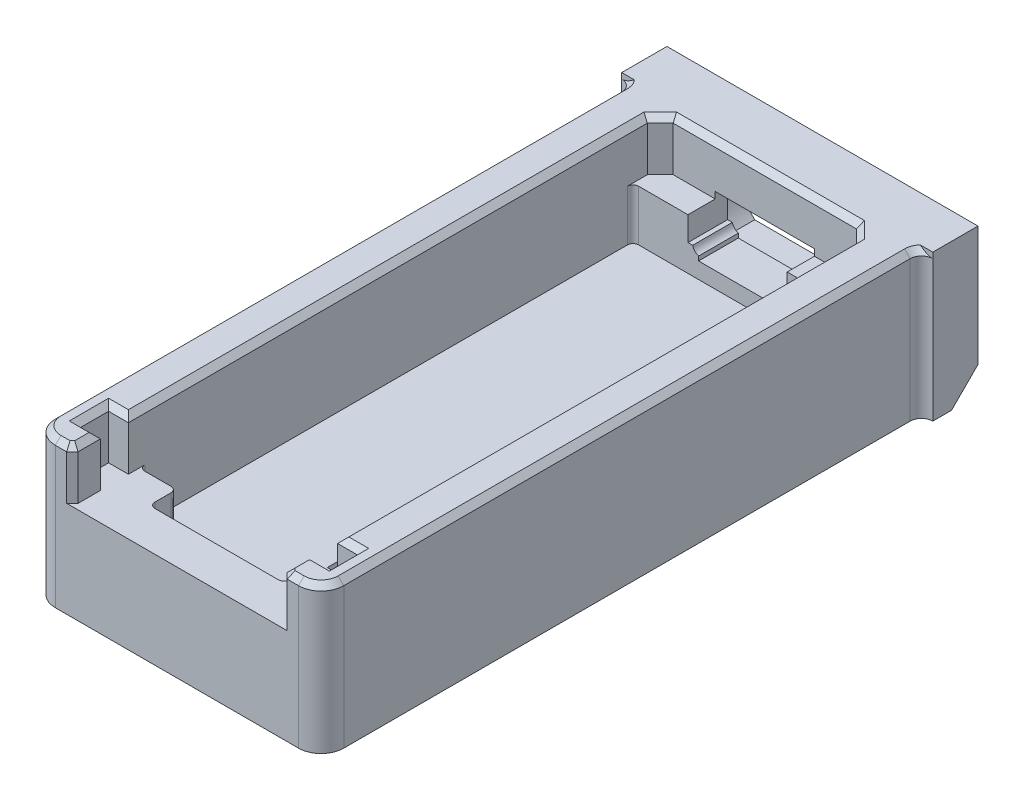
SolidWorks part; units mm, degrees
ref_plane "Front Plane" through (0, 0, 0) normal (0, 0, 1) x (1, 0, 0)
ref_plane "Top Plane" through (0, 0, 0) normal (0, 1, 0) x (1, 0, 0)
ref_plane "Right Plane" through (0, 0, 0) normal (1, 0, 0) x (0, 0, -1)
sketch "Sketch2" plane through (15.9134, 30.6185, 37.0903) normal (1, 0, 0) x (0, 0, 1)
  line L0 (116.2262, -14.5431) -> (116.2262, 10)
  line L1 (116.2262, 10) -> (-29.35, 10)
  line L2 (-29.35, 10) -> (-29.35, -22.1724)
  line L3 (-29.35, -22.1724) -> (116.2262, -14.5431)
  line L4 (-61.6865, -4.4906) -> (-8.9589, -1.7273) construction
  line L5 (104.9423, -11.6296) -> (97.9519, -11.996) construction
  line L7 (87.1415, -12.4624) -> (72.162, -13.2474) construction
  line L8 (21.59, -17.5) -> (-21.59, -17.5) construction
  line L9 (21.59, -17.5) -> (21.59, -2.5) construction
  line L10 (21.59, -2.5) -> (-21.59, -2.5) construction
  line L11 (-21.59, -17.5) -> (-21.59, -2.5) construction
  line L12 (21.09, -2.5) -> (19.55, -2.5) construction
  line L13 (112.2262, -12.75) -> (112.2262, 6) construction
  line L14 (112.2262, 6) -> (-25.35, 6) construction
  line L15 (21.59, 0) -> (21.59, -2.5) construction
  line L16 (-21.59, 0) -> (-21.59, -2.5) construction
  line L18 (87.0734, -11.1642) -> (87.2095, -13.7606) construction
  line L19 (87.0734, -11.1642) -> (72.094, -11.9492) construction
  line L20 (87.2095, -13.7606) -> (72.2301, -14.5457) construction
  line L21 (72.094, -11.9492) -> (72.2301, -14.5457) construction
  line L22 (80.7932, -12.4747) -> (87.1247, -12.1428) construction
  line L24 (21.7261, -12.5361) -> (21.59, -9.9396) construction
  line L25 (21.7261, -12.5361) -> (36.7055, -11.751) construction
  line L26 (21.59, -9.9396) -> (36.5694, -9.1546) construction
  line L27 (36.7055, -11.751) -> (36.5694, -9.1546) construction
  line L28 (37.3995, -10.6632) -> (29.9098, -11.0557) construction
  line L30 (-25.35, 6) -> (-25.35, -19.96) construction
  line L31 (36.6375, -10.4528) -> (21.658, -11.2379) construction
  line L32 (29.8941, -10.7562) -> (29.8993, -10.856) construction
  line L33 (69.094, -2.4418) -> (69.094, -6.4491) construction
  line L34 (21.0682, 9.5) -> (21.3918, 9.5) construction
  line L35 (-25.35, 4.3272) -> (-25.35, 4.1272) construction
  line L36 (112.2262, -14.5431) -> (112.2262, 6) construction
  line L37 (-25.35, 6) -> (-25.35, -22.1724) construction
  line L38 (-25.35, -19.96) -> (112.2262, -12.75) construction
  line L39 (-29.4547, -20.1751) -> (116.1215, -12.5458) construction
  point P42 (29.8967, -10.8061)
  dimension "D2" = 32.5246
  dimension "D3" = 4
  dimension "D4" = 15
  dimension "D5" = 15
  dimension "D6" = 2.6
  dimension "D7" = 0.5
  dimension "D9" = 10.82
  dimension "D10" = 0.8318
  dimension "D11" = 7
  dimension "D12" = 0.3
  dimension "D13" = 3
  dimension "D14" = 0.5
  dimension "D8" = 2
extrude "Boss-Extrude1" add sketch "Sketch2" along normal mid plane 48
shell "Shell1" thickness 4 removed face at (15.9134, 48.9763, 80.5284)
fillet "Fillet1" radius 4 4 edges at (-8.0866, 36.7047, 7.7403) (39.9134, 36.7047, 7.7403) (-8.0866, 32.8901, 153.3164) (39.9134, 32.8901, 153.3164)
chamfer "Chamfer1" distance 2.3431 angle 45 8 edges at (-6.915, 20.6185, 152.1449) (15.9134, 20.6185, 153.3164) (38.7418, 20.6185, 152.1449) (39.9134, 20.6185, 80.5284) (38.7418, 20.6185, 8.9118) (15.9134, 20.6185, 7.7403) (-6.915, 20.6185, 8.9118) (-8.0866, 20.6185, 80.5284)
sketch "Sketch3" plane through (0, 24.6185, 0) normal (0, 1, 0) x (1, 0, 0)
  line L0 (18.8534, -58.0703) -> (18.3534, -58.0703) construction
  line L1 (18.1034, -57.8203) -> (19.1034, -57.8203)
  line L2 (18.1034, -57.8203) -> (18.1034, -58.8203)
  line L3 (18.1034, -58.8203) -> (19.1034, -58.8203)
  line L4 (19.1034, -57.8203) -> (19.1034, -58.8203)
  line L5 (18.8534, -58.5703) -> (18.8534, -58.0703) construction
  line L6 (20.6434, -57.8203) -> (20.6434, -58.8203)
  line L7 (20.6434, -57.8203) -> (21.6434, -57.8203)
  line L8 (21.6434, -57.8203) -> (21.6434, -58.8203)
  line L9 (20.6434, -58.8203) -> (21.6434, -58.8203)
  line L10 (20.6434, -55.2803) -> (20.6434, -56.2803)
  line L11 (20.6434, -55.2803) -> (21.6434, -55.2803)
  line L12 (21.6434, -55.2803) -> (21.6434, -56.2803)
  line L13 (20.6434, -56.2803) -> (21.6434, -56.2803)
  line L14 (20.6434, -52.7403) -> (20.6434, -53.7403)
  line L15 (20.6434, -52.7403) -> (21.6434, -52.7403)
  line L16 (21.6434, -52.7403) -> (21.6434, -53.7403)
  line L17 (20.6434, -53.7403) -> (21.6434, -53.7403)
  line L18 (18.1034, -55.2803) -> (18.1034, -56.2803)
  line L19 (18.1034, -55.2803) -> (19.1034, -55.2803)
  line L20 (19.1034, -55.2803) -> (19.1034, -56.2803)
  line L21 (18.1034, -56.2803) -> (19.1034, -56.2803)
  line L22 (18.1034, -52.7403) -> (18.1034, -53.7403)
  line L23 (18.1034, -52.7403) -> (19.1034, -52.7403)
  line L24 (19.1034, -52.7403) -> (19.1034, -53.7403)
  line L25 (18.1034, -53.7403) -> (19.1034, -53.7403)
  line L26 (20.8934, -58.5703) -> (21.3934, -58.5703) construction
  line L27 (20.8934, -55.5303) -> (20.8934, -56.0303) construction
  point P4 (18.6034, -57.8203)
  point P7 (18.6034, -58.0703)
  point P8 (19.1034, -58.3203)
  point P11 (18.8534, -58.3203)
  point P12 (21.1434, -58.8203)
  point P35 (21.1434, -58.5703)
  point P36 (20.6434, -55.7803)
  point P39 (20.8934, -55.7803)
  dimension "D1" = 1
  dimension "D2" = 2
  dimension "D3" = 3
extrude "Cut-Extrude1" cut sketch "Sketch3" against normal offset from surface (3.5 mm away) 0.5 up to face at (15.9134, 20.6185, 80.5284)
sketch "Sketch4" plane through (0, 0, 7.7403) normal (0, 0, -1) x (-1, 0, 0)
  line L0 (-13.2434, 28.9458) -> (-18.5834, 28.9458) construction
  line L1 (-13.2434, 28.9458) -> (-18.5834, 28.9458) construction
  line L2 (-9.9134, 31.5685) -> (-15.9134, 37.5685) construction
  line L3 (-15.9134, 28.9458) -> (-15.9134, 37.5381) construction
  line L4 (-21.9134, 31.5685) -> (-9.9134, 31.5685)
  line L5 (-21.9134, 31.5685) -> (-21.9134, 24.1685) construction
  line L6 (-21.9134, 24.1685) -> (-9.9134, 24.1685)
  line L7 (-9.9134, 31.5685) -> (-9.9134, 24.1685) construction
  line L8 (-19.1134, 26.7913) -> (-18.5834, 28.9458) construction
  arc A0 (-19.5034, 27.1813) -> (-19.1134, 26.7913) centre (-19.1134, 27.1813) ccw construction
  arc A1 (-19.5034, 27.1813) -> (-19.1134, 26.7913) centre (-19.1134, 27.1813) ccw construction
  arc A2 (-12.7134, 26.7913) -> (-12.3234, 27.1813) centre (-12.7134, 27.1813) ccw construction
  arc A3 (-12.7134, 26.7913) -> (-12.3234, 27.1813) centre (-12.7134, 27.1813) ccw construction
  arc A4 (-9.9134, 24.1685) -> (-9.9134, 31.5685) centre (-13.6134, 27.8685) ccw
  arc A5 (-21.9134, 24.1685) -> (-21.9134, 31.5685) centre (-18.2134, 27.8685) cw
  point P12 (-15.9134, 31.5685)
  point P13 (-15.9134, 28.9458)
  point P17 (-21.9134, 27.8685)
  point P20 (-18.8484, 27.8685)
  dimension "D3" = 45
  dimension "D1" = 12
  dimension "D2" = 7.4
extrude "Cut-Extrude2" cut sketch "Sketch4" against normal up to surface (4 mm away) up to face at (15.9134, 38.5999, 11.7403)
sketch "Sketch5" plane through (0, 24.6185, 0) normal (0, 1, 0) x (1, 0, 0)
  line L0 (11.5234, -11.7403) -> (11.5234, -15.0865)
  line L1 (35.9134, -11.7403) -> (-4.0866, -11.7403) construction
  line L2 (23.9134, -61.0903) -> (7.9134, -61.0903) construction
  line L3 (11.5234, -15.2503) -> (7.1634, -15.2503)
  line L4 (6.6634, -15.7503) -> (6.6634, -58.4303)
  line L5 (7.1634, -58.9303) -> (9.4634, -58.9303)
  line L6 (9.9634, -59.4303) -> (9.9634, -60.8403)
  line L7 (10.4634, -61.3403) -> (21.3634, -61.3403)
  line L8 (26.6734, -64.8503) -> (5.1534, -64.8503)
  line L9 (3.1534, -62.8503) -> (3.1534, -12.7403)
  line L10 (2.1534, -11.7403) -> (11.5234, -11.7403)
  line L11 (6.9134, -60.0903) -> (6.9134, -14.0903) construction
  line L12 (9.0534, -15.5003) -> (7.5134, -15.5003) construction
  line L13 (15.9134, 2.8046) -> (15.9134, 8.9631) construction
  line L14 (35.9134, -7.7403) -> (-4.0866, -7.7403) construction
  line L15 (11.8234, -11.9003) -> (11.8234, -11.7403) construction
  line L16 (6.6634, -58.9303) -> (3.1534, -58.9303) construction
  line L17 (9.9634, -61.3403) -> (9.9634, -64.8503) construction
  line L18 (7.5134, -58.6803) -> (9.0534, -58.6803) construction
  line L19 (10.2134, -59.0903) -> (10.2134, -53.0903) construction
  line L20 (9.3434, -15.2503) -> (9.3434, -11.7403) construction
  line L21 (22.4834, -15.2503) -> (22.4834, -11.7403) construction
  line L22 (21.8634, -61.3403) -> (21.8634, -64.8503) construction
  line L23 (25.1634, -58.9303) -> (28.6734, -58.9303) construction
  line L24 (29.6734, -11.7403) -> (20.3034, -11.7403)
  line L25 (28.6734, -62.8503) -> (28.6734, -12.7403)
  line L28 (25.1634, -15.7503) -> (25.1634, -58.4303)
  line L29 (20.3034, -15.2503) -> (24.6634, -15.2503)
  line L30 (20.3034, -11.7403) -> (20.3034, -15.0865)
  line L31 (11.5234, -15.2503) -> (11.5234, -15.0865)
  line L32 (20.3034, -15.2503) -> (20.3034, -15.0865)
  line L33 (21.8634, -60.8403) -> (21.8634, -59.9938)
  line L34 (21.8634, -59.9938) -> (22.927, -58.9303)
  line L35 (22.927, -58.9303) -> (24.6634, -58.9303)
  line L36 (21.9134, -59.5903) -> (22.4134, -59.0903) construction
  arc A1 (7.1634, -15.2503) -> (6.6634, -15.7503) centre (7.1634, -15.7503) ccw
  arc A2 (6.6634, -58.4303) -> (7.1634, -58.9303) centre (7.1634, -58.4303) ccw
  arc A3 (9.4634, -58.9303) -> (9.9634, -59.4303) centre (9.4634, -59.4303) cw
  arc A4 (9.9634, -60.8403) -> (10.4634, -61.3403) centre (10.4634, -60.8403) ccw
  arc A5 (5.1534, -64.8503) -> (3.1534, -62.8503) centre (5.1534, -62.8503) cw
  arc A6 (3.1534, -12.7403) -> (2.1534, -11.7403) centre (2.1534, -12.7403) ccw
  arc A7 (28.6734, -12.7403) -> (29.6734, -11.7403) centre (29.6734, -12.7403) cw
  arc A8 (26.6734, -64.8503) -> (28.6734, -62.8503) centre (26.6734, -62.8503) ccw
  arc A9 (21.8634, -60.8403) -> (21.3634, -61.3403) centre (21.3634, -60.8403) cw
  arc A11 (25.1634, -58.4303) -> (24.6634, -58.9303) centre (24.6634, -58.4303) cw
  arc A12 (24.6634, -15.2503) -> (25.1634, -15.7503) centre (24.6634, -15.7503) cw
  point P9 (15.9134, -61.3403)
  point P18 (15.9134, -7.7403)
  point P77 (15.9134, -64.8503)
  dimension "D1" = 0.25
  dimension "D7" = 0.5
  dimension "D8" = 2
  dimension "D9" = 2
  dimension "D2" = 0.25
  dimension "D3" = 0.3
  dimension "D4" = 0.25
  dimension "D5" = 0.25
  dimension "D6" = 0.25
  dimension "D10" = 0.25
extrude "Boss-Extrude2" add sketch "Sketch5" along normal up to surface (4.5 mm away)
sketch "Sketch7" plane through (0, 0, 11.7403) normal (0, 0, -1) x (-1, 0, 0)
  line L1 (-20.3034, 24.6185) -> (-11.5234, 24.6185) construction
  line L2 (-20.3034, 24.6185) -> (-11.5234, 24.6185)
  line L3 (-19.3634, 26.0413) -> (-12.4634, 26.0413)
  line L4 (-11.5234, 26.9813) -> (-11.9388, 26.9813)
  line L5 (-11.5234, 29.1185) -> (-11.5234, 24.6185) construction
  line L6 (-15.9134, 24.6185) -> (-15.9134, 31.8855) construction
  line L7 (-18.9134, 26.2913) -> (-12.9134, 26.2913) construction
  line L9 (-12.7134, 26.5913) -> (-12.7134, 26.6313) construction
  line L10 (-12.4634, 26.0413) -> (-12.4634, 26.4214)
  line L11 (-12.1234, 27.1813) -> (-12.0234, 27.1813) construction
  line L12 (-11.5234, 26.9813) -> (-11.5234, 24.6185)
  line L13 (-20.3034, 26.9813) -> (-20.3034, 24.6185)
  line L14 (-19.3634, 26.0413) -> (-19.3634, 26.4214)
  line L15 (-20.3034, 26.9813) -> (-19.888, 26.9813)
  arc A1 (-19.3634, 26.4214) -> (-19.888, 26.9813) centre (-19.1134, 27.1813) cw
  arc A2 (-12.7134, 26.3813) -> (-11.9134, 27.1813) centre (-12.7134, 27.1813) ccw
  arc A3 (-12.4634, 26.4214) -> (-11.9388, 26.9813) centre (-12.7134, 27.1813) ccw
  point P7 (-15.9134, 24.6185)
  point P12 (-15.9134, 24.6185)
  point P30 (-15.9134, 26.0413)
  dimension "D1" = 0.25
  dimension "D3" = 0.25
  dimension "D4" = 0.2
  dimension "D2" = 0.25
extrude "Boss-Extrude5" add sketch "Sketch7" against normal up to surface (3.51 mm away) contours A1 L15 L13 L2 L12 L4 A3 L10 L3 L14 up to face at (9.3434, 26.8685, 15.2503)
sketch "Sketch9" plane through (0, 29.1185, 0) normal (0, 1, 0) x (1, 0, 0)
  line L0 (28.6734, -62.8503) -> (28.6734, -12.7403)
  line L1 (20.3034, -12.8403) -> (24.017, -12.8403)
  line L2 (24.017, -12.8403) -> (25.1634, -13.9867)
  line L3 (25.1634, -13.9867) -> (25.1634, -60.1938)
  line L5 (23.2945, -11.7403) -> (20.3034, -11.7403)
  line L6 (29.6734, -11.7403) -> (23.2945, -11.7403)
  line L7 (20.3034, -11.7403) -> (20.3034, -12.8403)
  line L8 (11.5234, -11.7403) -> (11.5234, -15.2503) construction
  line L9 (11.5234, -11.7403) -> (11.5234, -12.8403)
  line L10 (15.9134, -11.7403) -> (15.9134, -10.4554) construction
  line L11 (25.1634, -60.1938) -> (25.1634, -64.8503)
  line L12 (2.1534, -11.7403) -> (8.5323, -11.7403) construction
  line L13 (8.5323, -11.7403) -> (11.5234, -11.7403) construction
  line L14 (2.1534, -11.7403) -> (8.5323, -11.7403)
  line L15 (8.5323, -11.7403) -> (11.5234, -11.7403)
  line L16 (25.1634, -13.9867) -> (24.017, -12.8403)
  line L17 (25.1634, -60.1938) -> (25.1634, -13.9867)
  line L18 (24.017, -61.3403) -> (25.1634, -60.1938)
  line L19 (6.6634, -60.1938) -> (7.8098, -61.3403)
  line L20 (7.8098, -61.3403) -> (24.017, -61.3403)
  line L21 (6.6634, -13.9867) -> (6.6634, -60.1938)
  line L22 (7.8098, -12.8403) -> (6.6634, -13.9867)
  line L23 (24.017, -12.8403) -> (7.8098, -12.8403)
  line L29 (6.6634, -13.9867) -> (6.6634, -60.1938)
  line L30 (7.8098, -12.8403) -> (6.6634, -13.9867)
  line L31 (11.5234, -12.8403) -> (7.8098, -12.8403)
  line L32 (3.1534, -62.8503) -> (3.1534, -12.7403) construction
  line L33 (3.1534, -62.8503) -> (3.1534, -12.7403)
  line L35 (26.6734, -64.8503) -> (5.1534, -64.8503) construction
  line L36 (35.9134, -7.7403) -> (-4.0866, -7.7403) construction
  line L37 (25.1634, -64.8503) -> (26.6734, -64.8503)
  line L40 (6.6634, -60.1938) -> (6.6634, -64.8503)
  line L41 (6.6634, -64.8503) -> (5.1534, -64.8503)
  arc A0 (3.1534, -12.7403) -> (2.1534, -11.7403) centre (2.1534, -12.7403) ccw construction
  arc A1 (3.1534, -12.7403) -> (2.1534, -11.7403) centre (2.1534, -12.7403) ccw
  arc A2 (3.1534, -62.8503) -> (5.1534, -64.8503) centre (5.1534, -62.8503) ccw construction
  arc A3 (3.1534, -62.8503) -> (5.1534, -64.8503) centre (5.1534, -62.8503) ccw
  arc A4 (28.6734, -62.8503) -> (26.6734, -64.8503) centre (26.6734, -62.8503) cw
  arc A5 (28.6734, -12.7403) -> (29.6734, -11.7403) centre (29.6734, -12.7403) cw
  point P29 (15.9134, -7.7403)
  point P34 (15.9134, -64.8503)
  point P35 (15.9134, -61.3403)
  dimension "D1" = 0.25
extrude "Boss-Extrude6" add sketch "Sketch9" along normal offset from surface (4.45 mm away) 2 up to face at (15.9134, 31.5685, 9.7403) offset beyond the face yes
sketch "Sketch10" plane through (0, 0, 11.7403) normal (0, 0, -1) x (-1, 0, 0)
  line L0 (-20.3034, 31.5685) -> (-20.3034, 26.9813) construction
  line L1 (-20.3034, 33.5685) -> (-11.5234, 33.5685)
  line L2 (-20.3034, 33.5685) -> (-20.3034, 29.6958)
  line L3 (-20.3034, 29.6958) -> (-11.5234, 29.6958)
  line L4 (-11.5234, 33.5685) -> (-11.5234, 29.6958)
  line L5 (-11.5234, 31.5685) -> (-11.5234, 26.9813) construction
  line L6 (-11.5234, 33.5685) -> (-2.1534, 33.5685) construction
  line L7 (-13.4434, 29.4458) -> (-18.3834, 29.4458) construction
  dimension "D1" = 0.25
extrude "Boss-Extrude7" add sketch "Sketch10" against normal up to surface (1.1 mm away) up to face at (22.1602, 31.3435, 12.8403)
chamfer "Chamfer2" distance 0.5 angle 45 2 edges at (6.6634, 31.3435, 64.8503) (25.1634, 31.3435, 64.8503)
sketch "Sketch11" plane through (0, 33.5685, 0) normal (0, 1, 0) x (1, 0, 0)
  line L0 (22.007, -12.8403) -> (25.1634, -15.9967)
  line L1 (7.8098, -12.8403) -> (24.017, -12.8403) construction
  line L2 (25.1634, -13.9867) -> (25.1634, -64.3503) construction
  line L3 (24.017, -12.8403) -> (25.1634, -13.9867) construction
  line L4 (24.8134, -16.0003) -> (24.3134, -15.5003) construction
  line L5 (24.017, -12.8403) -> (25.1634, -13.9867)
  line L6 (25.1634, -13.9867) -> (25.1634, -15.9967)
  line L7 (22.007, -12.8403) -> (24.017, -12.8403)
  line L8 (15.9134, -11.7403) -> (15.9134, 3.1456) construction
  line L10 (35.9134, -11.7403) -> (-4.0866, -11.7403) construction
  line L11 (9.8198, -12.8403) -> (7.8098, -12.8403)
  line L12 (6.6634, -13.9867) -> (6.6634, -15.9967)
  line L13 (7.8098, -12.8403) -> (6.6634, -13.9867)
  line L14 (9.8198, -12.8403) -> (6.6634, -15.9967)
  point P13 (15.9134, -11.7403)
  dimension "D1" = 0.25
extrude "Boss-Extrude8" [suppressed] add sketch "Sketch11" against normal offset from surface (2.7 mm away) 0.25
sketch "Sketch12" plane through (0, 33.5685, 0) normal (0, 1, 0) x (1, 0, 0)
  line L0 (15.9134, -57.4103) -> (15.9134, -59.8903) construction
  line L7 (25.6634, -64.8503) -> (6.1634, -64.8503) construction
  line L9 (15.9134, -59.8903) -> (15.9134, -62.3703) construction
  line L10 (15.9134, -62.3703) -> (15.9134, -64.8503) construction
  line L11 (28.6734, -62.8503) -> (26.9184, -62.8503) construction
  line L12 (26.9184, -59.8903) -> (4.9084, -59.8903)
  line L13 (26.9184, -59.8903) -> (26.9184, -62.3703)
  line L14 (26.9184, -62.3703) -> (4.9084, -62.3703)
  line L15 (4.9084, -59.8903) -> (4.9084, -62.3703)
  line L16 (26.9184, -62.8503) -> (25.1634, -62.8503) construction
  line L17 (25.1634, -13.9867) -> (25.1634, -64.3503) construction
  line L18 (19.3734, -59.5903) -> (17.8334, -59.5903) construction
  point P16 (15.9134, -59.8903)
  dimension "D1" = 0.3
extrude "Cut-Extrude3" cut sketch "Sketch12" against normal up to surface (4.45 mm away) up to face at (15.9551, 29.1185, 60.9424)
chamfer "Chamfer3" distance 0.5 angle 45 23 edges at (28.9663, 33.5685, 12.0332) (28.6734, 33.5685, 37.7953) (28.0876, 33.5685, 64.2645) (26.1684, 33.5685, 64.8503) (6.4134, 33.5685, 64.6003) (25.4134, 33.5685, 64.6003) (25.1634, 33.5685, 63.3603) (26.0409, 33.5685, 62.3703) (26.9184, 33.5685, 61.1303) (26.0409, 33.5685, 59.8903) (25.1634, 33.5685, 36.9385) (15.9134, 33.5685, 12.8403) (6.6634, 33.5685, 36.9385) (5.7859, 33.5685, 59.8903) (4.9084, 33.5685, 61.1303) (5.7859, 33.5685, 62.3703) (6.6634, 33.5685, 63.3603) (5.6584, 33.5685, 64.8503) (3.7392, 33.5685, 64.2645) (3.1534, 33.5685, 37.7953) (2.8605, 33.5685, 12.0332) (24.5902, 33.5685, 13.4135) (7.2366, 33.5685, 13.4135)
sketch "Sketch13" plane through (0, 33.5685, 0) normal (0, 1, 0) x (1, 0, 0)
  line L0 (2.1534, -11.7403) -> (2.1534, -7.7403)
  line L1 (35.9134, -7.7403) -> (-4.0866, -7.7403) construction
  line L2 (2.1534, -7.7403) -> (29.6734, -7.7403)
  line L3 (29.6734, -7.7403) -> (29.6734, -11.7403)
  line L8 (35.9134, -11.7403) -> (29.6734, -11.7403)
  line L9 (28.6734, -12.7403) -> (28.6734, -62.8503)
  line L10 (26.6734, -64.8503) -> (5.1534, -64.8503)
  line L11 (3.1534, -62.8503) -> (3.1534, -12.7403)
  line L12 (2.1534, -11.7403) -> (-4.0866, -11.7403)
  line L13 (-4.0866, -11.7403) -> (-4.0866, -149.3164)
  line L14 (-4.0866, -149.3164) -> (35.9134, -149.3164)
  line L15 (35.9134, -149.3164) -> (35.9134, -11.7403)
  line L17 (28.6734, -12.7403) -> (28.6734, -62.8503)
  line L18 (26.6734, -64.8503) -> (5.1534, -64.8503)
  line L19 (3.1534, -62.8503) -> (3.1534, -12.7403)
  arc A4 (29.6734, -11.7403) -> (28.6734, -12.7403) centre (29.6734, -12.7403) ccw
  arc A5 (26.6734, -64.8503) -> (28.6734, -62.8503) centre (26.6734, -62.8503) ccw
  arc A6 (3.1534, -62.8503) -> (5.1534, -64.8503) centre (5.1534, -62.8503) ccw
  arc A7 (3.1534, -12.7403) -> (2.1534, -11.7403) centre (2.1534, -12.7403) ccw
  arc A8 (29.6734, -11.7403) -> (28.6734, -12.7403) centre (29.6734, -12.7403) ccw
  arc A9 (26.6734, -64.8503) -> (28.6734, -62.8503) centre (26.6734, -62.8503) ccw
  arc A10 (3.1534, -62.8503) -> (5.1534, -64.8503) centre (5.1534, -62.8503) ccw
  arc A11 (3.1534, -12.7403) -> (2.1534, -11.7403) centre (2.1534, -12.7403) ccw
  dimension "D1" = 0
extrude "Boss-Extrude9" add sketch "Sketch13" against normal up to surface (12.95 mm away) separate body up to face at (15.9134, 20.6185, 80.5284)
combine bodies "Combine1" operation type common bodies to combine 109 110 109
equation "\"D1@Chamfer1\"=(2*((2*4^2)^(1/2)-4)^2)^(1/2)"
